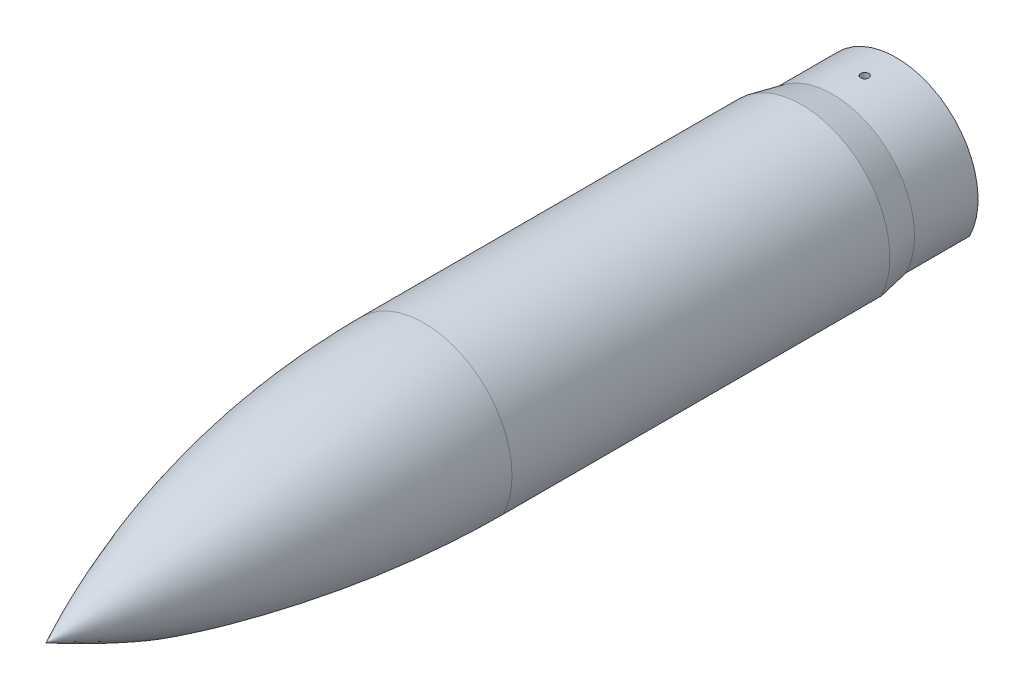
SolidWorks part; units mm, degrees
ref_plane "Front Plane" through (0, 0, 0) normal (0, 0, 1) x (1, 0, 0)
ref_plane "Top Plane" through (0, 0, 0) normal (0, 1, 0) x (1, 0, 0)
ref_plane "Right Plane" through (0, 0, 0) normal (1, 0, 0) x (0, 0, -1)
sketch "Sketch1" plane through (0, 0, 0) normal (1, 0, 0) x (0, 0, -1)
  line L0 (0, 0) -> (110.0352, 0) construction
  line L1 (152.4, 17.78) -> (76.2, 17.78)
  line L2 (152.4, 15.24) -> (76.2, 15.24)
  line L3 (152.4, 17.78) -> (158.6419, 16.51)
  line L4 (152.4, 15.24) -> (171.45, 15.24)
  line L5 (5.9274, 0) -> (0, 0)
  line L7 (158.6419, 16.51) -> (171.45, 16.51)
  line L8 (171.45, 16.51) -> (171.45, 15.24)
  arc A0 (76.2, 17.78) -> (0, 0) centre (76.2, -154.3957) ccw
  arc A1 (76.2, 15.24) -> (5.9274, 0) centre (76.2, -154.3957) ccw
  dimension "D1" = 2.54
  dimension "D2" = 76.2
  dimension "D3" = 76.2
  dimension "D4" = 15.24
  dimension "D5" = 19.05
  dimension "D6" = 1.27
  dimension "D7" = 6.2419
revolve "Revolve1" add sketch "Sketch1" angle 360 about L0
sketch "Sketch2" plane through (0, 0, -171.45) normal (0, 0, -1) x (-1, 0, 0)
  line L0 (14.0394, -5.9291) -> (-14.0394, -5.9291) construction
  line L1 (-14.8584, -3.3891) -> (14.8584, -3.3891) construction
  circle A0 centre (0, -86.4471) radius 80.518
  circle A1 centre (0, 0) radius 15.24 construction
  arc A2 (-14.8584, -3.3891) -> (-13.5013, -7.0691) centre (0, 0) ccw construction
  arc A3 (13.5013, -7.0691) -> (14.8584, -3.3891) centre (0, 0) ccw construction
  point P9 (0, 0)
  point P10 (0, 0)
  point P11 (0, 0)
  point P12 (0, 0)
  point P13 (0, 0)
  dimension "D3" = 161.036
  dimension "D1" = 2.54
  dimension "D2" = 29.7168
extrude "Cut-Extrude2" cut sketch "Sketch2" against normal up to vertex (171.45 mm away) up to point (0, 0, 0)
sketch "Sketch3" plane through (0, 0, 0) normal (0, 1, 0) x (1, 0, 0)
  line L0 (16.51, 171.45) -> (-16.51, 171.45) construction
  circle A0 centre (0, 165.1) radius 0.8001
  point P4 (0, 0)
  dimension "D1" = 1.6002
  dimension "D2" = 6.35
extrude "Cut-Extrude3" cut sketch "Sketch3" along normal up to surface (16.51 mm away) up to face at (0, 4.6038, -165.0459)
